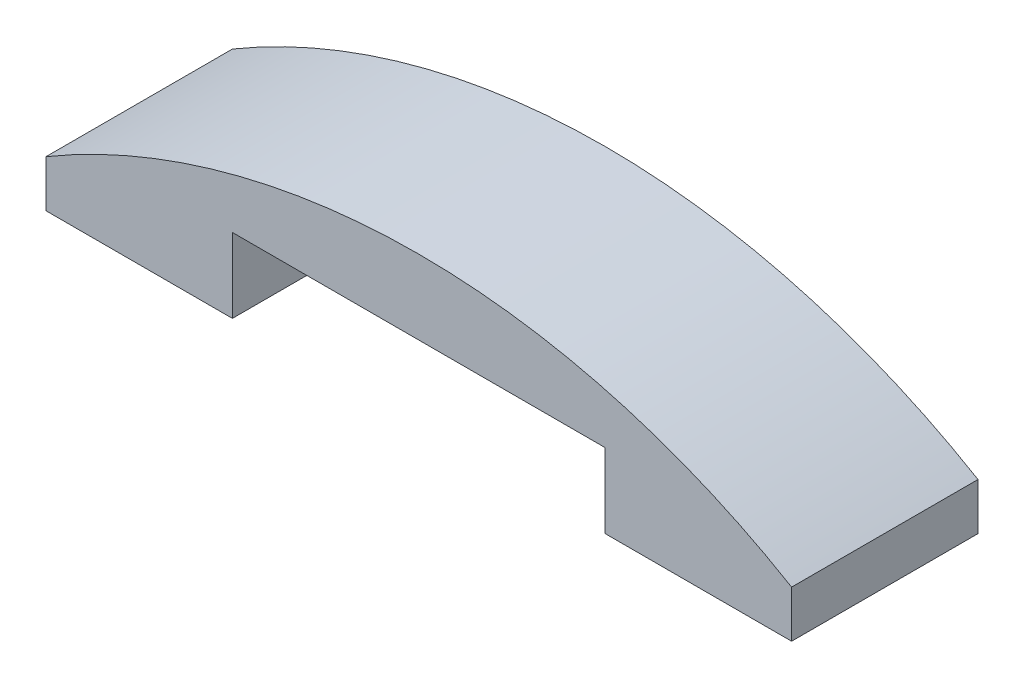
SolidWorks part; units mm, degrees
ref_plane "Front Plane" through (0, 0, 0) normal (0, 0, 1) x (1, 0, 0)
ref_plane "Top Plane" through (0, 0, 0) normal (0, 1, 0) x (1, 0, 0)
ref_plane "Right Plane" through (0, 0, 0) normal (1, 0, 0) x (0, 0, -1)
sketch "Sketch1" plane through (0, 0, 0) normal (0, 0, 1) x (1, 0, 0)
  line L0 (-7.95, 0) -> (-7.95, 3.175)
  line L1 (-7.95, 3.175) -> (7.95, 3.175)
  line L2 (7.95, 3.175) -> (7.95, 0)
  line L3 (7.95, 0) -> (15.9, 0)
  line L4 (-7.95, 0) -> (-15.9, 0)
  line L5 (0, 0) -> (0, 6.35) construction
  line L6 (-15.9, 0) -> (-15.9, 2)
  line L7 (15.9, 0) -> (15.9, 2)
  arc A2 (-15.9, 2) -> (15.9, 2) centre (0, -24.8836) cw
  point P10 (0, 3.175)
  dimension "D1" = 15.9
  dimension "D4" = 2
  dimension "D2" = 7.95
  dimension "D5" = 6.35
extrude "Boss-Extrude1" add sketch "Sketch1" along normal blind 7.95
shell "Shell1" thickness 0.7 removed face at (11.925, 0, 3.975) removed face at (0, 3.175, 3.975) removed face at (-11.925, 0, 3.975)
ref_plane "Plane1" through (0, 6.375, 0) normal (0, -1, 0) x (-1, 0, 0)
sketch "Sketch2" plane through (0, 6.375, 0) normal (0, -1, 0) x (-1, 0, 0)
  circle A0 centre (0, -3.975) radius 1.55
  circle A1 centre (0, -3.975) radius 0.55
  dimension "D2" = 3.1
  dimension "D3" = 1.1
  dimension "D1" = 3.975
extrude "Boss-Extrude2" add sketch "Sketch2" along normal up to surface (3.2 mm away) up to face at (0, 3.175, 0.35)
sketch "Sketch3" plane through (0, 6.375, 0) normal (0, -1, 0) x (-1, 0, 0)
  circle A1 centre (0, -3.975) radius 1.55
  circle A2 centre (0, -3.975) radius 1.55
  dimension "D1" = 0
extrude "Cut-Extrude1" cut sketch "Sketch3" along normal up to surface (0.025 mm away) up to face at (0, 4.175, 3.975)
